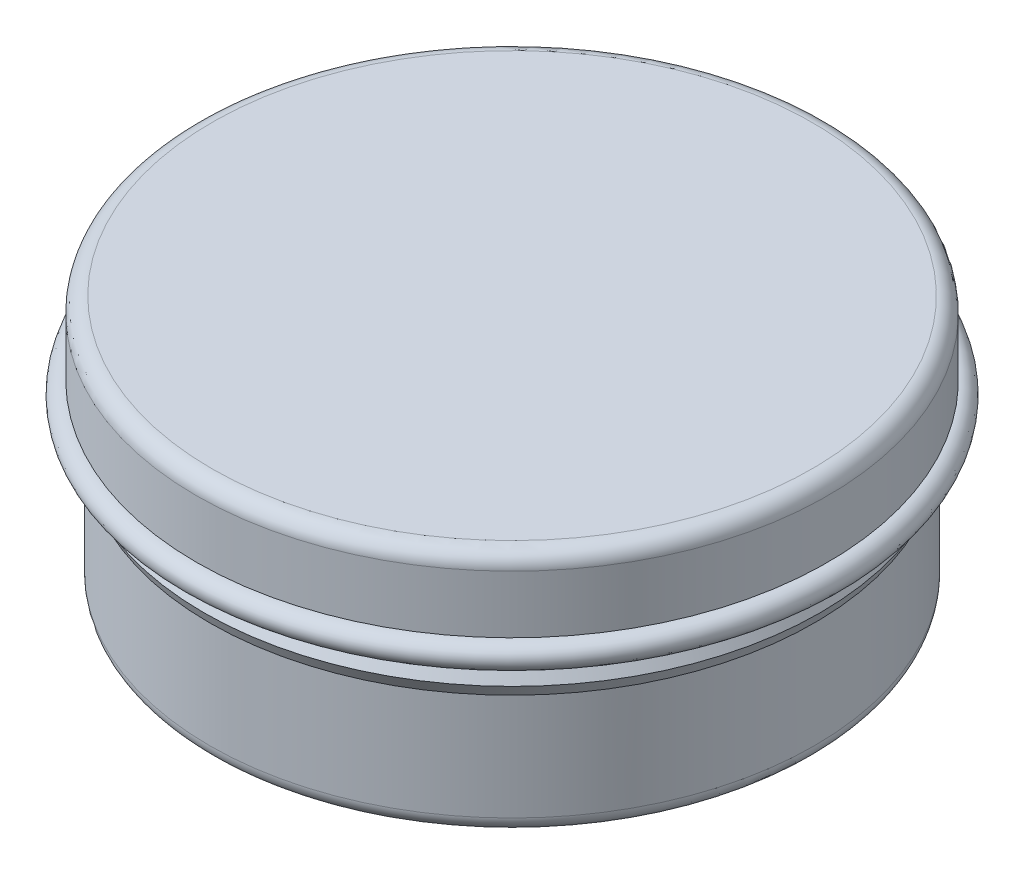
SolidWorks part; units mm, degrees
ref_plane "Front Plane" through (0, 0, 0) normal (0, 0, 1) x (1, 0, 0)
ref_plane "Top Plane" through (0, 0, 0) normal (0, 1, 0) x (1, 0, 0)
ref_plane "Right Plane" through (0, 0, 0) normal (1, 0, 0) x (0, 0, -1)
ref_axis "Axis1" through (-33.0333, 0, 0) along (1, 0, 0)
ref_axis "Axis2" through (0, 24.5224, 0) along (0, -1, 0)
ref_axis "Axis3" through (0, 0, -30.7663) along (0, 0, 1)
sketch "Sketch1" plane through (0, 0, 0) normal (0, 0, 1) x (1, 0, 0)
  line L22 (0, 0) -> (-19.45, 0)
  line L28 (-19.45, 0) -> (-19.45, 7.84)
  line L29 (-19.45, 7.84) -> (-19.825, 8.5975)
  line L30 (-19.825, 8.5975) -> (-19.45, 9.3551)
  line L31 (-19.45, 9.3551) -> (-19.45, 10.04)
  line L32 (-19.45, 10.04) -> (-20.3, 10.04)
  line L33 (-20.3, 11.64) -> (-20.3, 16.35)
  line L34 (-20.3, 16.35) -> (0, 16.35)
  line L35 (0, 16.35) -> (0, 0)
  line L36 (-21.2, 10.84) -> (-20.3, 10.84) construction
  line L37 (-19.45, 9.3551) -> (-19.45, 7.84) construction
  line L38 (-19.825, 8.5975) -> (-19.45, 8.5975) construction
  ellipse E0 centre (-20.3, 10.84) end of major axis (-21.2, 10.84) minor radius 0.8 (-20.3, 11.64) -> (-20.3, 10.04) ccw
  dimension "D2" = 20.3
  dimension "D1" = 19.45
  dimension "D3" = 16.35
  dimension "D4" = 1.5151
  dimension "D5" = 1.6
  dimension "D6" = 4.71
  dimension "D7" = 21.2
  dimension "D8" = 19.825
  dimension "D9" = 0.6849
revolve "Revolve1" add sketch "Sketch1" angle 360 about axis through (0, 24.5224, 0) along (0, -1, 0)
fillet "Fillet1" radius 1 2 edges at (0, 16.35, 20.3) (0, 0, 19.45)
scale "Scale1" scale about origin uniform scaling no x scale factor 1.05 y scale factor 1.05 z scale factor 1.05
